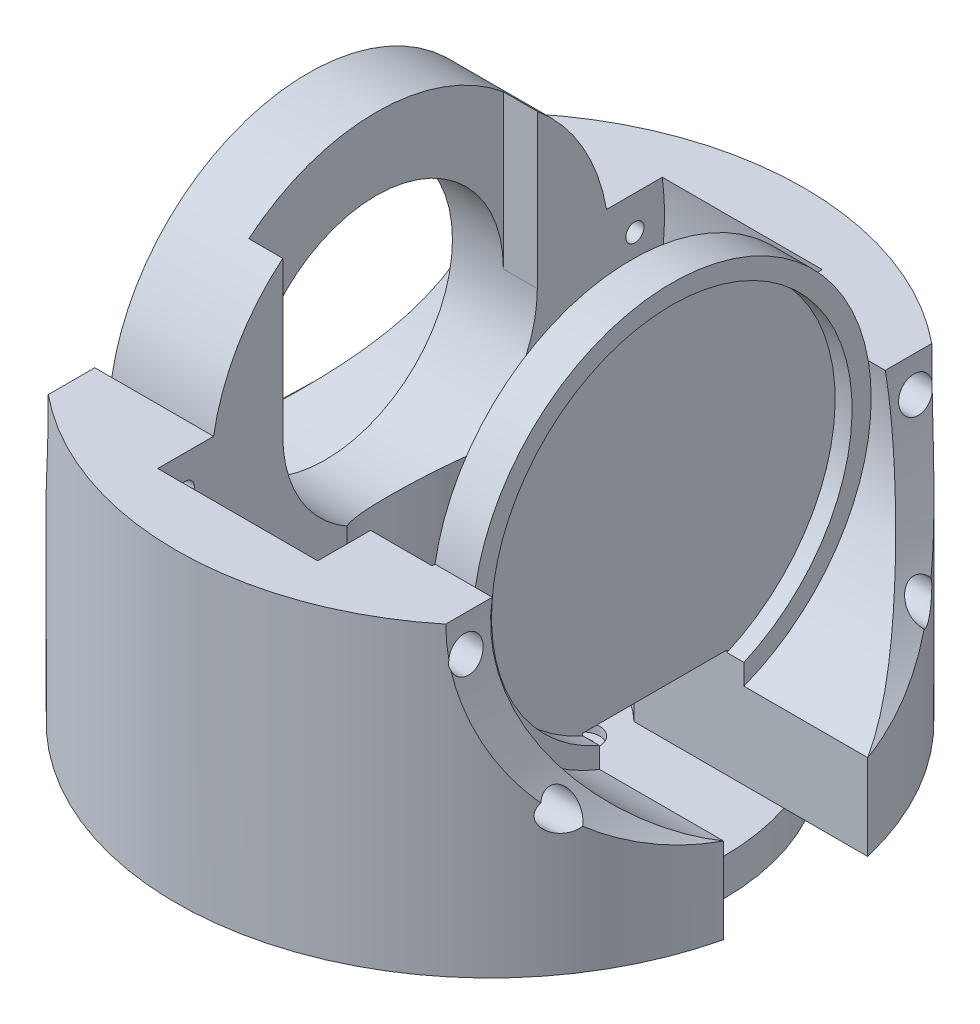
SolidWorks part; units mm, degrees
ref_plane "前视基准面" through (0, 0, 0) normal (0, 0, 1) x (1, 0, 0)
ref_plane "上视基准面" through (0, 0, 0) normal (0, 1, 0) x (1, 0, 0)
ref_plane "右视基准面" through (0, 0, 0) normal (1, 0, 0) x (0, 0, -1)
sketch "草图1" plane through (0, 0, 0) normal (0, 1, 0) x (1, 0, 0)
  circle A0 centre (0, 0) radius 56
  circle A1 centre (0, 0) radius 10
extrude "凸台-拉伸1" add sketch "草图1" along normal blind 5
sketch "草图2" plane through (0, 0, 0) normal (0, -1, 0) x (1, 0, 0)
  circle A0 centre (0, 0) radius 56
  circle A1 centre (0, 0) radius 45
extrude "凸台-拉伸2" add sketch "草图2" along normal blind 5.7
sketch "草图3" plane through (0, 5, 0) normal (0, 1, 0) x (1, 0, 0)
  line L0 (-13.8564, 8) -> (13.8564, -8) construction
  line L1 (13.8564, 8) -> (-13.8564, -8) construction
  line L2 (0, 16) -> (0, -16) construction
  circle A0 centre (0, 0) radius 16 construction
  arc A1 (0, 16) -> (13.8564, 8) centre (0, 0) cw construction
  point P5 (13.8564, -8)
  point P6 (0, 16)
  point P7 (13.8564, 8)
  point P8 (13.8564, 8)
  point P9 (0, -16)
  point P10 (-13.8564, -8)
  point P11 (-13.8564, 8)
hole_wizard "M4 六角圆柱头螺钉的柱形沉头孔1" positions "草图3" profile "草图4" counterbore size "M4" standard "GB" end condition through all
sketch "草图4" plane through (-13.8564, 5, -8) normal (1, 0, 0) x (0, 0, 1)
  line L0 (0, 0) -> (0, 10.7)
  line L1 (0, 10.7) -> (2.15, 10.7)
  line L3 (2.15, 10.7) -> (2.15, 2)
  line L4 (2.15, 2) -> (4, 2)
  line L5 (4, 2) -> (4, 0)
  line L7 (4, 0) -> (0, 0)
  line L11 (0, -6.35) -> (0, 107.95) construction
  dimension "通孔孔直径" = 4.3
  dimension "通孔孔深度" = 10.7
  dimension "柱形沉头孔直径" = 8
  dimension "柱形沉头孔深度" = 2
sketch "草图5" plane through (0, 5, 0) normal (0, 1, 0) x (1, 0, 0)
  circle A0 centre (0, 0) radius 74
  circle A1 centre (0, 0) radius 24
extrude "凸台-拉伸3" add sketch "草图5" along normal blind 4
sketch "草图7" plane through (0, 9, 0) normal (0, 1, 0) x (1, 0, 0)
  circle A0 centre (0, 0) radius 24
  circle A1 centre (0, 0) radius 74
extrude "凸台-拉伸4" add sketch "草图7" along normal blind 120
sketch "草图8" plane through (0, 0, 0) normal (1, 0, 0) x (0, 0, -1)
  line L0 (46.3141, 77) -> (74, 77)
  line L1 (74, 5) -> (74, 129) construction
  line L4 (-74, 129) -> (74, 9) construction
  line L8 (-74, 77) -> (-74, 129)
  line L9 (-74, 129) -> (74, 129)
  line L10 (74, 129) -> (74, 77)
  line L12 (-60.5, 77) -> (-74, 77)
  line L13 (-60.5, 77) -> (-46.3141, 77)
  arc A0 (-46.3141, 77) -> (46.3141, 77) centre (0, 69) cw
extrude "切除-拉伸1" cut sketch "草图8" along normal through all both and the other way through all
sketch "草图14" plane through (0, 0, 0) normal (1, 0, 0) x (0, 0, -1)
  line L1 (74, 5) -> (74, 77) construction
  line L2 (74, 9) -> (0, 9) construction
  arc A1 (0, 9) -> (0, 129) centre (0, 69) ccw
  arc A2 (0, 129) -> (0, 9) centre (0, 69) ccw
  point P0 (37, 9)
extrude "切除-拉伸2" cut sketch "草图14" against normal blind 18.85 and the other way blind 18.85
sketch "草图15" plane through (0, 0, 0) normal (1, 0, 0) x (0, 0, -1)
  line L0 (-47, 69) -> (-47, 77)
  line L1 (-74, 77) -> (-74, 5) construction
  line L2 (-74, 9) -> (74, 9) construction
  line L3 (74, 5) -> (74, 77) construction
  line L4 (-59.4643, 77) -> (-46.3141, 77) construction
  line L6 (47, 69) -> (47, 77)
  line L7 (46.3141, 77) -> (59.4643, 77) construction
  line L10 (-47, 77) -> (-47, 117.7352)
  line L11 (-47, 117.7352) -> (47, 117.7352)
  line L12 (47, 77) -> (47, 117.7352)
  arc A0 (-47, 69) -> (47, 69) centre (0, 69) ccw
  dimension "D1" = 8
extrude "切除-拉伸3" cut sketch "草图15" along normal blind 14.5 from offset 18.85
sketch "草图16" plane through (-18.85, 0, 0) normal (1, 0, 0) x (0, 0, -1)
  line L2 (-30, 69) -> (-30, 118.0849)
  line L3 (-30, 118.0849) -> (30, 118.0849)
  line L4 (30, 69) -> (30, 118.0849)
  arc A0 (-46.3141, 77) -> (46.3141, 77) centre (0, 69) ccw construction
  arc A1 (-30, 69) -> (30, 69) centre (0, 69) ccw
extrude "切除-拉伸4" cut sketch "草图16" against normal blind 8
sketch "草图18" plane through (-26.85, 0, 0) normal (1, 0, 0) x (0, 0, -1)
  arc A0 (-46.3141, 77) -> (46.3141, 77) centre (0, 69) ccw construction
  circle A1 centre (0, 69) radius 47
extrude "切除-拉伸5" cut sketch "草图18" against normal through all from offset 20 offset against normal yes
sketch "草图27" plane through (33.35, 0, 0) normal (-1, 0, 0) x (0, 0, 1)
  line L0 (0, 22) -> (0, 5) construction
  line L1 (-56, 5) -> (56, 5) construction
  line L2 (0, 22) -> (17, 22) construction
  line L3 (17, 22) -> (17, 25.1822)
  line L4 (17, 25.1822) -> (-17, 25.1822)
  line L6 (-17, 25.1822) -> (-17, 11.6422)
  line L8 (17, 11.4067) -> (17, 22)
  line L9 (-17, 11.6422) -> (-17, 5)
  line L10 (-17, 5) -> (17, 5)
  line L11 (17, 5) -> (17, 11.4067)
  arc A0 (-46.3141, 77) -> (46.3141, 77) centre (0, 69) ccw construction
extrude "切除-拉伸13" cut sketch "草图27" along normal up to next and the other way through all
sketch "草图30" plane through (-46.85, 0, 0) normal (-1, 0, 0) x (0, 0, 1)
  circle A0 centre (0, 69) radius 47 construction
  circle A1 centre (0, 69) radius 42
extrude "切除-拉伸14" cut sketch "草图30" against normal blind 8
sketch "草图31" plane through (33.35, 0, 0) normal (-1, 0, 0) x (0, 0, 1)
  circle A0 centre (0, 69) radius 42 construction
  circle A1 centre (0, 69) radius 47
extrude "切除-拉伸16" cut sketch "草图31" against normal up to next from offset 13.5 offset against normal yes
sketch "草图32" plane through (46.85, 0, 0) normal (1, 0, 0) x (0, 0, -1)
  circle A0 centre (0, 69) radius 42
extrude "切除-拉伸17" cut sketch "草图32" against normal blind 8
sketch "草图33" plane through (-38.85, 0, 0) normal (-1, 0, 0) x (0, 0, 1)
  circle A0 centre (0, 69) radius 30
extrude "切除-拉伸18" cut sketch "草图33" against normal up to next
sketch "草图34" plane through (0, 0, 0) normal (0, 0, 1) x (1, 0, 0)
  line L0 (-46.85, 116) -> (-46.85, 77) construction
  line L1 (57.7148, 77) -> (-57.7148, 77) construction
  line L2 (-18.85, 77) -> (-46.85, 77) construction
  line L3 (46.85, 116) -> (46.85, 77) construction
  line L4 (-46.85, 77) -> (-57.7148, 77)
  line L5 (-57.7148, 77) -> (-74, 22)
  line L6 (46.85, 77) -> (57.7148, 77)
  line L7 (57.7148, 77) -> (72.0208, 25.1822)
  arc A0 (-46.85, 77) -> (-74, 22) centre (-116.134, 77) cw
  arc A1 (46.85, 77) -> (72.0208, 25.1822) centre (112.7726, 77) ccw
extrude "切除-拉伸19" cut sketch "草图34" against normal through all and the other way through all
sketch "草图35" plane through (46.85, 0, 0) normal (1, 0, 0) x (0, 0, -1)
  line L0 (-17, 25.1822) -> (-17, 30.5943)
  line L1 (-17, 30.5943) -> (17, 30.5943)
  line L2 (17, 30.5943) -> (17, 25.1822)
  line L3 (17, 25.1822) -> (-17, 25.1822)
  circle A0 centre (0, 69) radius 42 construction
  circle A1 centre (0, 69) radius 42 construction
extrude "切除-拉伸20" cut sketch "草图35" against normal up to next
sketch "草图36" plane through (-46.85, 0, 0) normal (-1, 0, 0) x (0, 0, 1)
  line L0 (0, 69) -> (-53, 69) construction
  line L1 (0, 69) -> (53, 69) construction
  line L2 (53, 69) -> (42.8813, 69) construction
  line L3 (42.8813, 69) -> (42.8813, 37.8521) construction
  line L4 (42.8813, 37.8521) -> (-42.8813, 37.8521) construction
  circle A0 centre (0, 69) radius 53 construction
  point P5 (-53, 69)
  point P8 (53, 69)
  point P11 (-42.8813, 37.8521)
  point P16 (42.8813, 37.8521)
hole_wizard "M4 六角圆柱头螺钉的柱形沉头孔2" positions "草图36" profile "草图37" counterbore size "M4" standard "GB"
sketch "草图37" plane through (-46.85, 37.8521, 42.8813) normal (0, 1, 0) x (0, 0, 1)
  line L0 (0, 0) -> (0, 46.9919)
  line L1 (0, 46.9919) -> (2.15, 45.7)
  line L2 (2.15, 45.7) -> (2.15, 24)
  line L3 (2.15, 24) -> (4, 24)
  line L4 (4, 24) -> (4, 0)
  line L5 (4, 0) -> (0, 0)
  line L10 (0, 46.9919) -> (-2.15, 45.7) construction
  line L11 (0, -6.35) -> (0, 107.95) construction
  dimension "孔直径" = 4.3
  dimension "孔深度" = 45.7
  dimension "柱形沉头孔直径" = 8
  dimension "柱形沉头孔深度" = 24
  dimension "导头角度" = 118
sketch "草图38" plane through (-46.85, 0, 0) normal (-1, 0, 0) x (0, 0, 1)
  line L0 (-49, 69) -> (-53, 69) construction
  line L1 (-53, 69) -> (-53, 65) construction
  line L2 (-46.8798, 37.85) -> (-42.8798, 37.85) construction
  line L3 (-42.8798, 37.85) -> (-38.8798, 37.85) construction
  line L4 (0, 69) -> (53, 69) construction
  line L5 (38.8798, 37.85) -> (42.8798, 37.85) construction
  arc A1 (-45.107, 41.1726) -> (-40.4084, 34.7048) centre (0, 69) ccw construction
  circle A2 centre (-53, 69) radius 4
  circle A3 centre (-42.8798, 37.85) radius 4
  circle A4 centre (53, 69) radius 4
  circle A5 centre (42.8798, 37.85) radius 4
  arc A6 (40.4084, 34.7048) -> (52.8491, 72.9972) centre (0, 69) ccw construction
  arc A7 (-52.8491, 72.9972) -> (-52.8491, 65.0028) centre (0, 69) ccw construction
extrude "切除-拉伸23" cut sketch "草图38" along normal up to next
sketch "草图39" plane through (46.85, 0, 0) normal (1, 0, 0) x (0, 0, -1)
  line L0 (0, 69) -> (-53, 69) construction
  line L1 (0, 69) -> (53, 69) construction
  line L2 (53, 69) -> (53, 37.85) construction
  line L3 (53, 37.85) -> (42.8798, 37.85) construction
  line L4 (42.8798, 37.85) -> (-42.8798, 37.85) construction
  line L6 (53, 69) -> (53, 37.85) construction
  circle A0 centre (0, 69) radius 53 construction
  circle A1 centre (-53, 69) radius 4
  circle A2 centre (53, 69) radius 4
  circle A3 centre (42.8798, 37.85) radius 4
  circle A4 centre (-42.8798, 37.85) radius 4
extrude "切除-拉伸24" cut sketch "草图39" along normal up to next
sketch "草图40" plane through (46.85, 0, 0) normal (1, 0, 0) x (0, 0, -1)
  point P0 (-53, 69)
  point P1 (-42.8798, 37.85)
  point P3 (42.8798, 37.85)
  point P5 (53, 69)
hole_wizard "M4 六角圆柱头螺钉的柱形沉头孔3" positions "草图40" profile "草图41" counterbore size "M4" standard "GB"
sketch "草图41" plane through (46.85, 69, 53) normal (0, 1, 0) x (0, 0, -1)
  line L0 (0, 0) -> (0, 46.9919)
  line L1 (0, 46.9919) -> (2.15, 45.7)
  line L2 (2.15, 45.7) -> (2.15, 24)
  line L3 (2.15, 24) -> (4, 24)
  line L4 (4, 24) -> (4, 0)
  line L5 (4, 0) -> (0, 0)
  line L10 (0, 46.9919) -> (-2.15, 45.7) construction
  line L11 (0, -6.35) -> (0, 107.95) construction
  dimension "孔直径" = 4.3
  dimension "孔深度" = 45.7
  dimension "柱形沉头孔直径" = 8
  dimension "柱形沉头孔深度" = 24
  dimension "导头角度" = 118
sketch "草图42" plane through (0, -5.7, 0) normal (0, -1, 0) x (1, 0, 0)
  circle A0 centre (0, 0) radius 45
  circle A1 centre (0, 0) radius 56
extrude "切除-拉伸25" cut sketch "草图42" against normal blind 2 and the other way through all
sketch "草图43" plane through (38.85, 0, 0) normal (1, 0, 0) x (0, 0, -1)
  circle A0 centre (0, 69) radius 42.5
  dimension "D1" = 85
extrude "切除-拉伸26" cut sketch "草图43" along normal blind 12
sketch "草图44" plane through (-38.85, 0, 0) normal (-1, 0, 0) x (0, 0, 1)
  circle A0 centre (0, 69) radius 42.5
  dimension "D1" = 85
extrude "切除-拉伸27" cut sketch "草图44" along normal blind 12
sketch "草图45" plane through (46.85, 0, 0) normal (1, 0, 0) x (0, 0, -1)
  circle A0 centre (0, 69) radius 47
extrude "切除-拉伸28" cut sketch "草图45" against normal blind 4
sketch "草图46" plane through (0, -3.7, 0) normal (0, -1, 0) x (1, 0, 0)
  circle A0 centre (0, 0) radius 55
  circle A1 centre (0, 0) radius 56
extrude "切除-拉伸29" cut sketch "草图46" against normal up to surface (8.7 mm away) up to face at (-1.1555, 5, 0)
sketch "草图47" plane through (-46.85, 0, 0) normal (-1, 0, 0) x (0, 0, 1)
  circle A0 centre (0, 69) radius 47
extrude "切除-拉伸30" cut sketch "草图47" against normal blind 4
